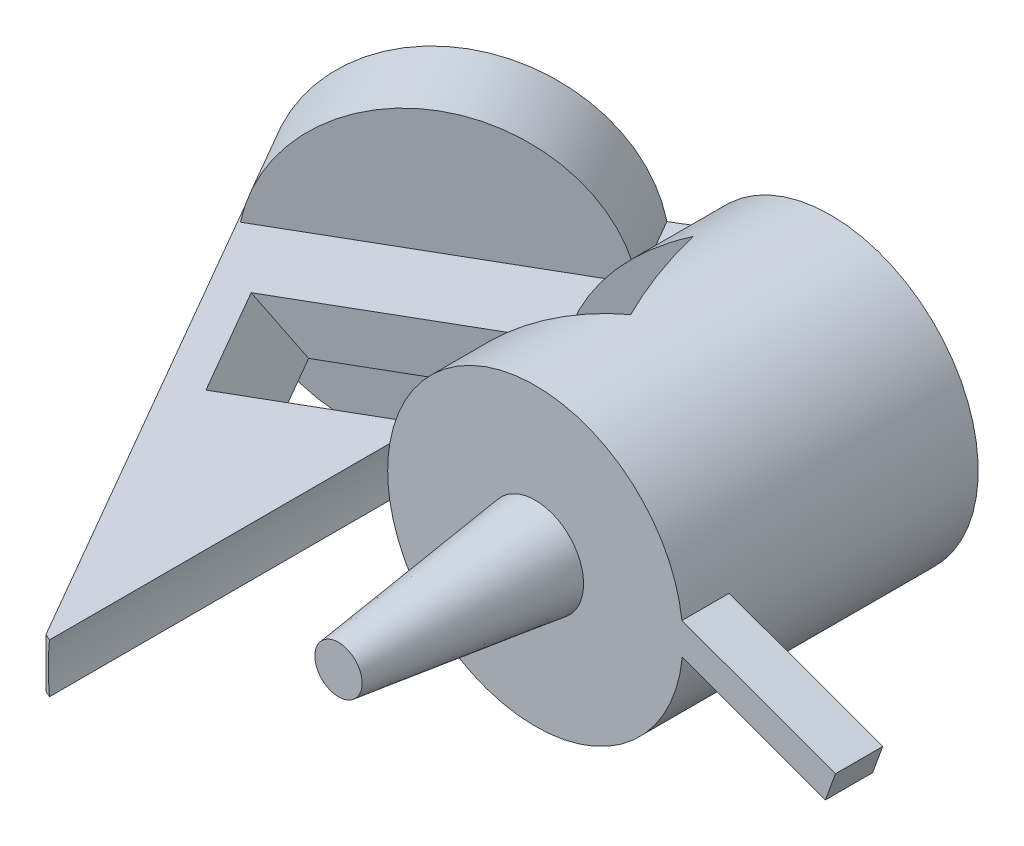
SolidWorks part; units mm, degrees
ref_plane "Front Plane" through (0, 0, 0) normal (0, 0, 1) x (1, 0, 0)
ref_plane "Top Plane" through (0, 0, 0) normal (0, 1, 0) x (1, 0, 0)
ref_plane "Right Plane" through (0, 0, 0) normal (1, 0, 0) x (0, 0, -1)
sketch "Sketch1" plane through (0, 0, 0) normal (0, 0, 1) x (1, 0, 0)
  line L0 (0, 0) -> (1.2826, 3.5238) construction
  line L5 (1.2826, 3.5238) -> (46.6088, -12.9735) construction
  line L6 (1.2826, 3.5238) -> (18.6539, -2.7988) construction
  line L7 (1.2826, 3.5238) -> (6.2305, 17.1183) construction
  line L8 (0, 0) -> (-31.7364, 0) construction
  line L9 (10.6795, 0.1036) -> (29.4734, -6.7368)
  line L10 (10.6795, 0.1036) -> (11.7056, 2.9227)
  line L11 (11.7056, 2.9227) -> (30.4994, -3.9177)
  line L12 (29.4734, -6.7368) -> (30.4994, -3.9177)
  line L13 (-3, 2.5) -> (-3, -2.5)
  line L14 (-50, 2.5) -> (0, 2.5)
  line L15 (-50, 2.5) -> (-50, -2.5)
  line L16 (-50, -2.5) -> (0, -2.5)
  line L17 (0, 2.5) -> (0, -2.5)
  circle A0 centre (0, 0) radius 4.9
  circle A1 centre (0, 0) radius 15
  circle A2 centre (0, 0) radius 2.4
  point P17 (-50, 0)
  point P18 (0, 0)
  dimension "D1" = 4.8
  dimension "D2" = 9.8
  dimension "D3" = 30
  dimension "D4" = 5
  dimension "D5" = 3.75
  dimension "D6" = 90
  dimension "D7" = 20
  dimension "D8" = 10
  dimension "D9" = 3
  dimension "D10" = 50
  dimension "D11" = 110
  dimension "D12" = 3
extrude "Boss-Extrude1" add sketch "Sketch1" against normal blind 15 and the other way blind 15 contours A1
extrude "Boss-Extrude2" add sketch "Sketch1<3>" against normal blind 4.8 from surface contours A2 starting at face at (15, 0, -15)
sketch "Sketch1<3>" plane through (0, 0, 0) normal (0, 0, 1) x (1, 0, 0) same geometry as "Sketch1"
ref_plane "Plane1" through (0, 0, 35) normal (0, 0, 1) x (1, 0, 0)
ref_plane "Plane2" through (0, 0, 15) normal (0, 0, 1) x (1, 0, 0)
sketch "Sketch4" plane through (0, 0, 15) normal (0, 0, 1) x (1, 0, 0)
  circle A0 centre (0, 0) radius 4.9
  circle A1 centre (0, 0) radius 4.9 construction
sketch "Sketch3" plane through (0, 0, 35) normal (0, 0, 1) x (1, 0, 0)
  circle A0 centre (0, 0) radius 2.4
  dimension "D1" = 4.8
loft "Loft2" add section "Sketch4" section "Sketch3" connector at (0.2431, 4.894, 15) connector at (0.2903, 2.3824, 35)
extrude "Boss-Extrude3" add sketch "Sketch1<5>" against normal blind 4.8 from surface contours L11 L12 L9 L10 starting at face at (15, 0, 15)
sketch "Sketch1<5>" plane through (0, 0, 0) normal (0, 0, 1) x (1, 0, 0) same geometry as "Sketch1"
extrude "Boss-Extrude4" add sketch "Sketch1<7>" along normal blind 60 contours A1 L14 L15 L16 region at (-32.4651, 0, 0)
sketch "Sketch1<7>" plane through (0, 0, 0) normal (0, 0, 1) x (1, 0, 0) same geometry as "Sketch1"
extrude "Boss-Extrude5" add sketch "Sketch1<8>" against normal blind 38 contours A1 L14 L15 L16 | L14 A1 L16 A0 | A2 L13 L14 A0 L16 region at (-9.8024, 0, 0) region at (-32.4651, 0, 0) region at (-3.8513, 0, 0)
sketch "Sketch1<8>" plane through (0, 0, 0) normal (0, 0, 1) x (1, 0, 0) same geometry as "Sketch1"
sketch "Sketch6" plane through (0, 0, 0) normal (0, 1, 0) x (1, 0, 0)
  line L0 (0, 31.0233) -> (0, -56.4767) construction
  line L1 (0, -56.4767) -> (-93.8788, -12.7002) construction
  line L2 (8.2583, -60.3276) -> (-33.0417, 11.2061) construction
  line L3 (-20.0513, 18.7061) -> (0, 31.0233) construction
  line L4 (0, -56.4767) -> (18.1191, -64.9257) construction
  line L5 (-15.4432, -49.2754) -> (39.4972, 68.5446)
  line L6 (-15.4432, -49.2754) -> (-46.0321, 3.7061) construction
  line L7 (-20.0513, 18.7061) -> (-46.0321, 3.7061) construction
  line L8 (39.4972, 68.5446) -> (29.5278, 73.1934)
  line L9 (29.5278, 73.1934) -> (0, 31.0233)
  point P14 (-33.0417, 11.2061)
  dimension "D1" = 65
  dimension "D2" = 35
  dimension "D3" = 25
  dimension "D4" = 82.6
  dimension "D5" = 30
  dimension "D6" = 87.5
  dimension "D7" = 130
  dimension "D8" = 11
  dimension "D9" = 100
sketch "Sketch7" plane through (0, 0, 0) normal (0, 1, 0) x (1, 0, 0)
  line L0 (-15.4432, -49.2754) -> (0, -56.4767)
  line L1 (0, -56.4767) -> (-93.8788, -12.7002) construction
  line L2 (-15.4432, -49.2754) -> (-46.0321, 3.7061) construction
  line L3 (-15.4432, -49.2754) -> (-46.0321, 3.7061)
  line L4 (-46.0321, 3.7061) -> (-20.0513, 18.7061)
  line L7 (0, 56.4517) -> (-64.9778, 56.4517)
  line L8 (-64.9778, 56.4517) -> (-64.9778, -114.6241)
  line L9 (-64.9778, -114.6241) -> (0, -114.6241)
  line L10 (0, -114.6241) -> (0, -56.4767)
  line L11 (0, 59.3803) -> (0, 15) construction
  line L12 (0, 15) -> (-17.9116, 15) construction
  line L13 (-14.7902, 15) -> (-3, 15) construction
  line L14 (0, 56.4517) -> (0, 31.0233)
  line L16 (-20.0513, 18.7061) -> (0, 31.0233)
  line L17 (-20.0513, 18.7061) -> (0, 31.0233) construction
  line L18 (-3, 29.1805) -> (-3, 15)
  line L19 (-8.25, 15) -> (-8.25, 25.9555)
  line L20 (-8.25, 15) -> (0, 15)
  line L23 (0, 31.0233) -> (0, -56.4767) construction
  line L26 (-3, 38) -> (-3, 15) construction
  dimension "D1" = 8.25
extrude "Cut-Extrude1" cut sketch "Sketch7" against normal through all both and the other way through all contours L4 L16 L14 L7 L8 L9 L10 L0 L3 | L19 L20 L14 L16 region at (-36.8024, 0, 33.858) region at (-5.5127, 0, -21.3185)
ref_plane "Plane3" through (-33.0417, 0, -11.2061) normal (-0.5, 0, -0.866) x (-0.866, 0, 0.5)
ref_plane "Plane4" through (0, 0, 0) normal (0, -1, 0) x (-0.866, 0, 0.5)
sketch "Sketch8" plane through (-33.0417, 0, -11.2061) normal (-0.5, 0, -0.866) x (-0.866, 0, 0.5)
  circle A0 centre (0, 0) radius 15
  dimension "D1" = 30
extrude "Boss-Extrude6" add sketch "Sketch8" against normal blind 8
ref_plane "Plane5" through (-17.5976, 7.3959, 10.16) normal (-0.8138, 0.342, 0.4698) x (-0.5, 0, -0.866)
sketch "Sketch10" plane through (-33.0417, 0, -11.2061) normal (-0.5, 0, -0.866) x (-0.866, 0, 0.5)
  line L0 (0, 47.2358) -> (0, -47.2358) construction
  line L2 (-42.5612, 0) -> (42.5612, 0) construction
  line L4 (5.2265, 0) -> (64.6397, 0) construction
  line L5 (0, 0) -> (32.388, 38.5985) construction
  point P5 (0, 0)
  point P10 (0, 0)
  dimension "D1" = 140
ref_plane "Plane7" through (-8.4057, 11.3643, 4.853) normal (0.5624, -0.7604, -0.3247) x (-0.5, 0, -0.866)
sketch "Sketch12" plane through (-8.4057, 11.3643, 4.853) normal (0.5624, -0.7604, -0.3247) x (-0.5, 0, -0.866)
  line L0 (9.9513, 2.6241) -> (-2.5987, 2.6241)
  line L1 (9.9513, 7.2741) -> (-2.5987, 7.2741)
  line L2 (9.9513, 7.2741) -> (9.9513, -24.8259)
  line L3 (9.9513, -24.8259) -> (-2.5987, -24.8259)
  line L4 (-2.5987, 7.2741) -> (-2.5987, -24.8259)
  line L5 (9.9513, -20.1759) -> (-2.5987, -20.1759)
  line L6 (3.6763, 2.6241) -> (3.6763, -20.1759) construction
  line L7 (3.6763, -8.7759) -> (9.9513, -8.7759) construction
  circle A0 centre (3.6763, 4.9441) radius 1
  circle A1 centre (3.6763, -22.4959) radius 1
  point P12 (9.9513, -8.7759)
  point P15 (0, 0)
  point P16 (0, 0)
  point P17 (3.6763, -8.7759)
  point P18 (0, 0)
  dimension "D4" = 2
  dimension "D5" = 2
  dimension "D1" = 12.55
  dimension "D2" = 32.1
  dimension "D3" = 22.8
  dimension "D6" = 2.33
  dimension "D7" = 2.33
extrude "Cut-Extrude4" cut sketch "Sketch12" along normal blind 18.3 from offset 5 contours L5 L2 L0 L4 region at (-16.023, 5.6648, 5.0059)
extrude "SERVO CUT" cut sketch "Sketch12<3>" against normal through all from offset 5 contours L2 L3 L4 L1
sketch "Sketch12<3>" plane through (-8.4057, 11.3643, 4.853) normal (0.5624, -0.7604, -0.3247) x (-0.5, 0, -0.866) same geometry as "Sketch12"
extrude "Cut-Extrude6" cut sketch "Sketch12<4>" along normal blind 5 from surface contours A0 region at (-6.988, 14.5752, -0.2105) starting at face at (-4.1725, 10.7764, -1.836)
sketch "Sketch12<4>" plane through (-8.4057, 11.3643, 4.853) normal (0.5624, -0.7604, -0.3247) x (-0.5, 0, -0.866) same geometry as "Sketch12"
ref_plane "Plane6" through (-11.6741, -11.3353, 6.74) normal (0.6628, 0.6436, -0.3827) x (-0.5, 0, -0.866)
